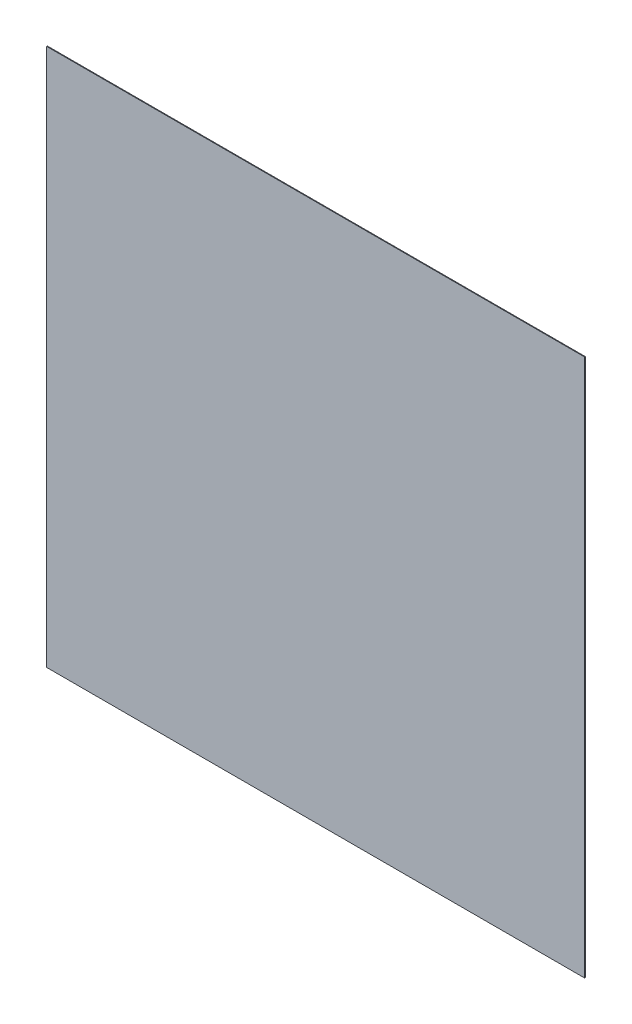
SolidWorks part; units mm, degrees
material "Polyethylene Cross-Linked"
ref_plane "Front Plane" through (0, 0, 0) normal (0, 0, 1) x (1, 0, 0)
ref_plane "Top Plane" through (0, 0, 0) normal (0, 1, 0) x (1, 0, 0)
ref_plane "Right Plane" through (0, 0, 0) normal (1, 0, 0) x (0, 0, -1)
sketch "Sketch1" plane through (0, 0, 0) normal (0, 0, 1) x (1, 0, 0)
  line L1 (-38.1, 38.1) -> (38.1, 38.1)
  line L2 (-38.1, 38.1) -> (-38.1, -38.1)
  line L3 (-38.1, -38.1) -> (38.1, -38.1)
  line L4 (38.1, 38.1) -> (38.1, -38.1)
  dimension "D1" = 76.2
  dimension "D2" = 76.2
  dimension "D3" = 38.1
  dimension "D4" = 38.1
extrude "Boss-Extrude1" add sketch "Sketch1" along normal blind 0.1
